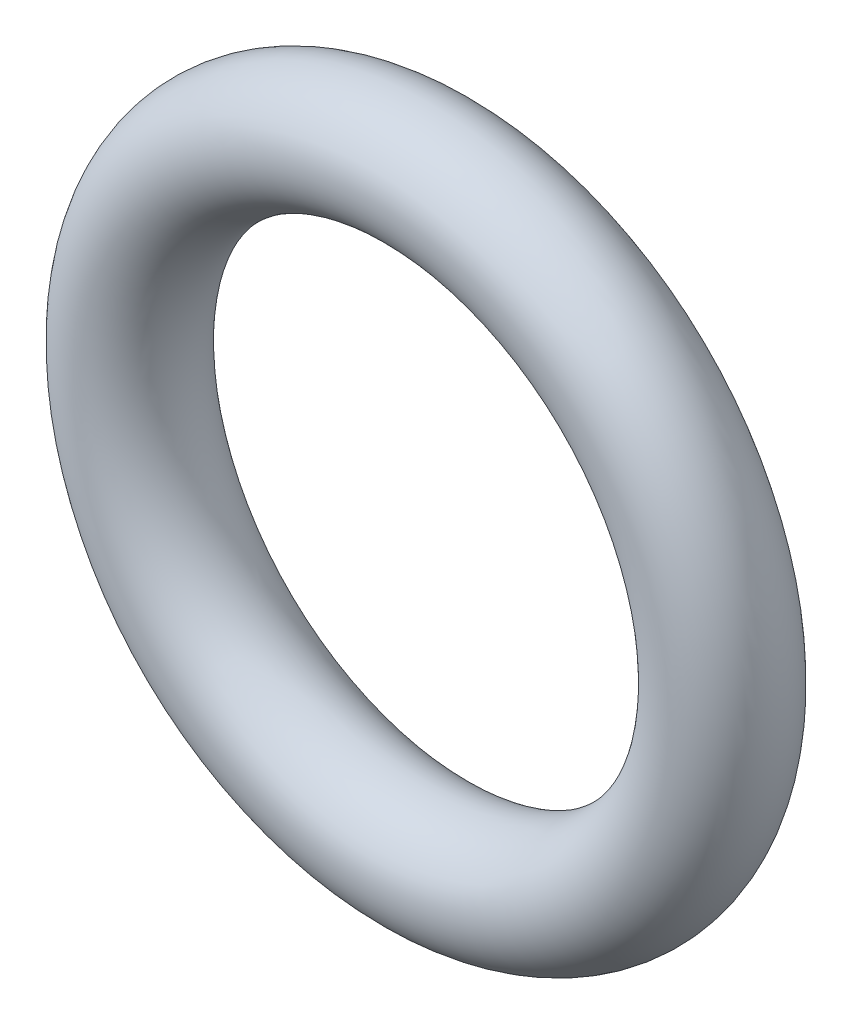
SolidWorks part; units mm, degrees
ref_plane "Front Plane" through (0, 0, 0) normal (0, 0, 1) x (1, 0, 0)
ref_plane "Top Plane" through (0, 0, 0) normal (0, 1, 0) x (1, 0, 0)
ref_plane "Right Plane" through (0, 0, 0) normal (1, 0, 0) x (0, 0, -1)
sketch "Sketch1" plane through (0, 0, 0) normal (1, 0, 0) x (0, 0, -1)
  circle A0 centre (0, 0) radius 1.6867
  dimension "D1" = 3.3734
sketch "Sketch2" plane through (0, 0, 0) normal (0, 0, 1) x (1, 0, 0)
  circle A0 centre (0, -8.4336) radius 8.4336
  point P3 (0, 0)
  dimension "D1" = 16.8672
sweep "Sweep1" add profiles "Sketch1" path "Sketch2"
